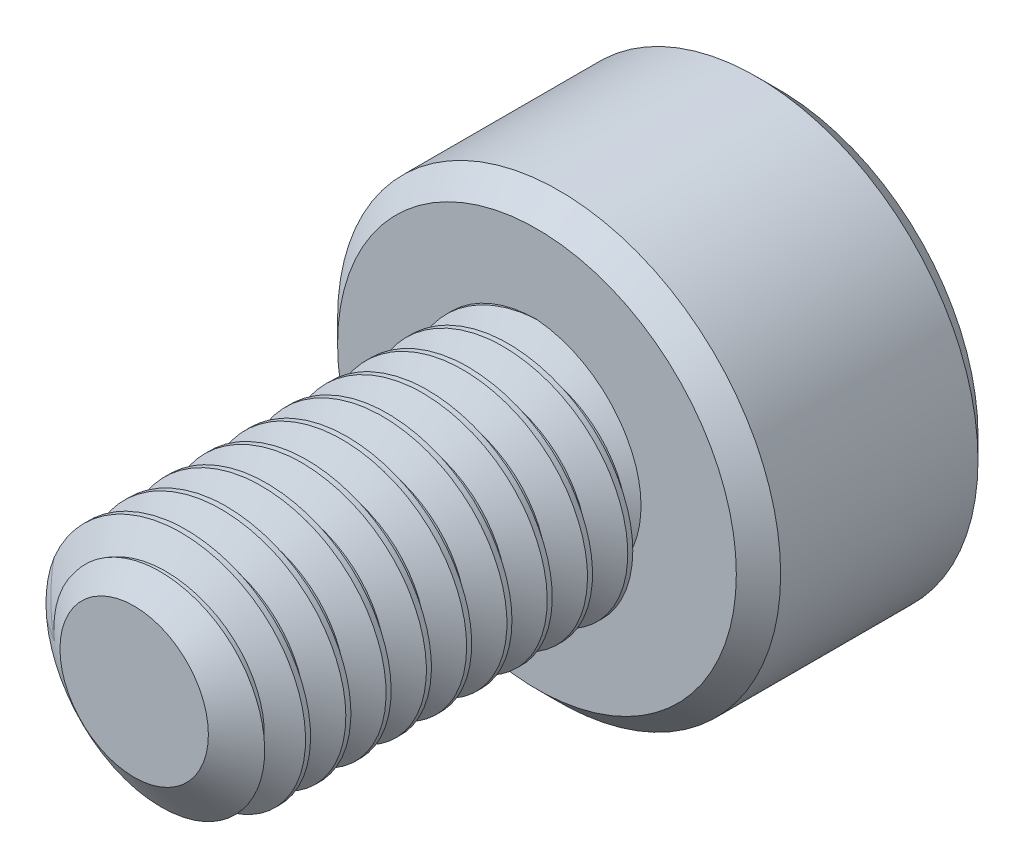
SolidWorks part; units mm, degrees
other "DetailItem1"
material "1.4310 (X10CrNi18-8)"
ref_plane "Front Plane" through (0, 0, 0) normal (0, 0, 1) x (1, 0, 0)
ref_plane "Top Plane" through (0, 0, 0) normal (0, 1, 0) x (1, 0, 0)
ref_plane "Right Plane" through (0, 0, 0) normal (1, 0, 0) x (0, 0, -1)
sketch "Sketch1" plane through (0, 0, 0) normal (0, 0, 1) x (1, 0, 0)
  circle A0 centre (0, 0) radius 1.5
  dimension "OD" = 3
extrude "Extrude1" add sketch "Sketch1" against normal blind 5
sketch "Sketch2" plane through (0, 0, 0) normal (0, 0, 1) x (1, 0, 0)
  circle A0 centre (0, 0) radius 1.5 construction
  circle A1 centre (0, 0) radius 1.5
curve "Helix/Spiral1" pitch 0.5 height 5.5 radius 1.5 centre (0, 0, 0) axis (0, 0, -1) start towards (0, 1, 0) parameters "pitch"=0.5
sketch "Sketch3" plane through (0, 0, 0) normal (1, 0, 0) x (0, 0, -1)
  line L0 (-0.4375, 1.5) -> (-0.25, 1.1752)
  line L1 (-0.25, 1.1752) -> (-0.1875, 1.1752)
  line L2 (-0.1875, 1.1752) -> (0, 1.5)
  line L3 (-0.4375, 1.5) -> (0, 1.5)
  line L4 (-0.2187, 1.5) -> (-0.2188, 1.1752) construction
  line L5 (-0.3438, 1.3376) -> (-0.0938, 1.3376) construction
  line L6 (0, 1.5) -> (0, -1.5) construction
  dimension "D1" = 0.0625
  dimension "D2" = 0.25
  dimension "D3" = 60
sweep "Cut-Sweep1" cut profiles "Sketch3" path "Helix/Spiral1" align with end faces yes
sketch "Sketch4" plane through (0, 0, 0) normal (1, 0, 0) x (0, 0, -1)
  line L0 (0.4053, 1.5) -> (0, 0.9212)
  line L1 (0, 0.9212) -> (0, 1.5)
  line L2 (0.4053, 1.5) -> (0, 1.5)
  line L3 (-0.4375, 1.5) -> (0, 1.5) construction
  line L4 (0, 0) -> (7.0209, 0) construction
  dimension "D1" = 55
  dimension "D2" = 0.254
revolve "Cut-Revolve1" cut sketch "Sketch4" angle 360 about L4
sketch "Sketch6" plane through (0, 0, -5) normal (0, 0, -1) x (-1, 0, 0)
  circle A0 centre (0, 0) radius 2.75
  dimension "head dia" = 5.5
extrude "Extrude2" add sketch "Sketch6" along normal blind 3
sketch "Sketch7" plane through (0, 0, -8) normal (0, 0, -1) x (-1, 0, 0)
  line L1 (0, 1.4434) -> (-1.25, 0.7217)
  line L2 (-1.25, 0.7217) -> (-1.25, -0.7217)
  line L3 (-1.25, -0.7217) -> (0, -1.4434)
  line L4 (0, -1.4434) -> (1.25, -0.7217)
  line L5 (1.25, -0.7217) -> (1.25, 0.7217)
  line L6 (1.25, 0.7217) -> (0, 1.4434)
  circle A0 centre (0, 0) radius 1.25 construction
  dimension "hex dia" = 2.5
extrude "Cut-Extrude1" cut sketch "Sketch7" against normal blind 1.875
sketch "Sketch8" plane through (0, 0, -8) normal (0, 0, -1) x (-1, 0, 0)
  circle A0 centre (0, 0) radius 1.4434
extrude "Cut-Extrude2" cut sketch "Sketch8" against normal through all draft 45
chamfer "Chamfer1" distance 0.275 angle 45 2 edges at (-2.75, 0, -8) (-2.75, 0, -5)
sketch "Sketch10" plane through (0, 0, -5) normal (0, 0, 1) x (1, 0, 0)
  circle A1 centre (0, 0) radius 1.5
  circle A2 centre (0, 0) radius 1.5
  dimension "D1" = 0
ref_plane "Plane1" through (0, 0, 0) normal (0, 0, 1) x (1, 0, 0)
extrude "partial thread" [suppressed] add sketch "Sketch10" along normal up to surface (4 mm away) separate body up to plane "Plane1"
chamfer "Chamfer2" [suppressed] distance 0.06 angle 45
combine bodies "Combine1" [suppressed] operation type add bodies to combine 107 108
sketch "Sketch9" plane through (0, 0, 0) normal (1, 0, 0) x (0, 0, -1)
  line L0 (0, 1.5) -> (0, -1.5) construction
  line L1 (1.25, 1.5) -> (1.25, -1.5) construction
  dimension "D1" = 1.25
equation "\"D3@Helix/Spiral1\" = \"screw length@Extrude1\"+\"pitch@Helix/Spiral1\""
equation "\"D1@Sketch3\" = \"pitch@Helix/Spiral1\"*.125"
equation "\"D2@Sketch3\" = \"pitch@Helix/Spiral1\"*.5"
equation "\"D1@Cut-Extrude1\" = \"hex dia@Sketch7\"*.75"
equation "\"D1@Chamfer1\" = \"head dia@Sketch6\"*.05"
equation "\"D1@Sketch9\" = \"pitch@Helix/Spiral1\"*2.5"
equation "\"D1@Chamfer2\"=\"OD@Sketch1\"*.02"
